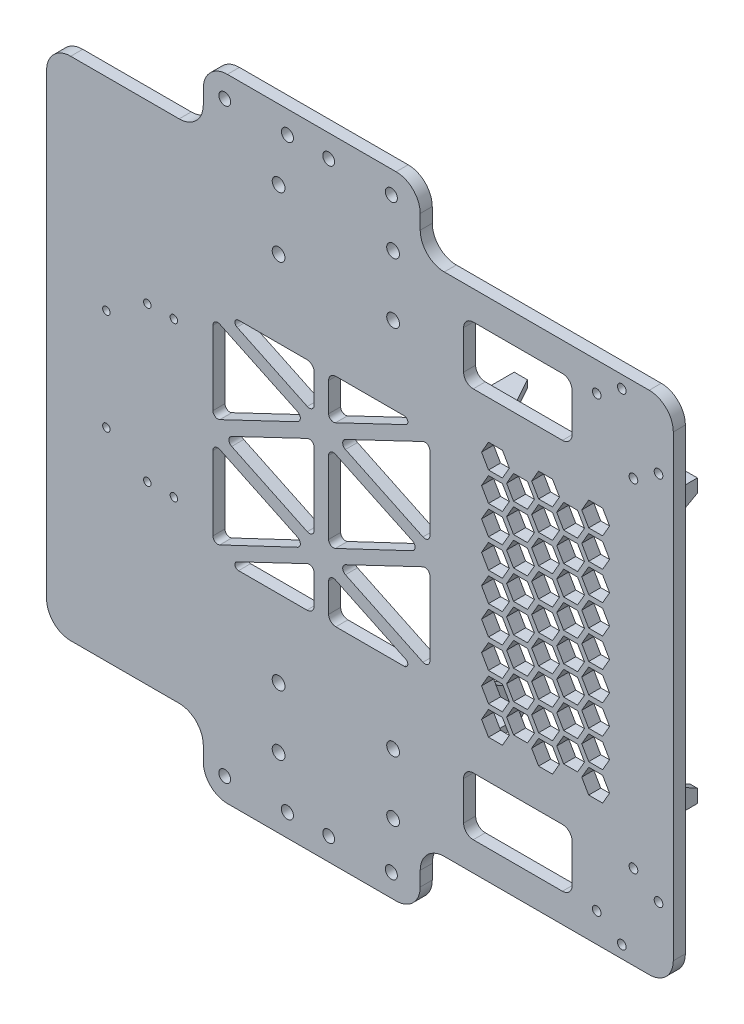
SolidWorks part; units mm, degrees
ref_plane "前视基准面" through (0, 0, 0) normal (0, 0, 1) x (1, 0, 0)
ref_plane "上视基准面" through (0, 0, 0) normal (0, 1, 0) x (1, 0, 0)
ref_plane "右视基准面" through (0, 0, 0) normal (1, 0, 0) x (0, 0, -1)
sketch "草图1" plane through (0, 0, 0) normal (0, 0, 1) x (1, 0, 0)
  line L2 (-130, 95) -> (-130, -95)
  line L3 (-120, -105) -> (-75, -105)
  line L4 (130, 95) -> (130, -95)
  line L5 (126.7518, 102.3765) -> (130, 105) construction
  line L6 (-130, -105) -> (-126.7518, -102.3765) construction
  line L9 (-65, -115) -> (-65, -121)
  line L10 (-55, -131) -> (15, -131)
  line L11 (25, -121) -> (25, -115)
  line L13 (35, -105) -> (120, -105)
  line L14 (126.7518, -102.3765) -> (130, -105) construction
  line L15 (-130, 105) -> (-126.7518, 102.3765) construction
  line L16 (-130, 0) -> (130, 0) construction
  line L17 (35, 105) -> (120, 105)
  line L18 (25, 121) -> (25, 115)
  line L19 (-55, 131) -> (15, 131)
  line L20 (-65, 115) -> (-65, 121)
  line L21 (-120, 105) -> (-75, 105)
  arc A1 (-120, -105) -> (-130, -95) centre (-120, -95) cw
  arc A3 (120, -105) -> (130, -95) centre (120, -95) ccw
  arc A8 (-65, -115) -> (-75, -105) centre (-75, -115) ccw
  arc A9 (25, -115) -> (35, -105) centre (35, -115) cw
  arc A10 (-55, -131) -> (-65, -121) centre (-55, -121) cw
  arc A11 (15, -131) -> (25, -121) centre (15, -121) ccw
  arc A12 (15, 131) -> (25, 121) centre (15, 121) cw
  arc A13 (-55, 131) -> (-65, 121) centre (-55, 121) ccw
  arc A14 (25, 115) -> (35, 105) centre (35, 115) ccw
  arc A15 (-65, 115) -> (-75, 105) centre (-75, 115) cw
  arc A16 (120, 105) -> (130, 95) centre (120, 95) cw
  arc A17 (-120, 105) -> (-130, 95) centre (-120, 95) ccw
  point P0 (0, 0)
  point P40 (25, -105)
  point P45 (25, 105)
  dimension "D2" = 10
  dimension "D3" = 65
  dimension "D4" = 10
  dimension "D5" = 105
  dimension "D7" = 10
  dimension "D8" = 10
  dimension "D10" = 10
  dimension "D12" = 10
  dimension "D13" = 105
  dimension "D18" = 90
  dimension "D19" = 6
extrude "凸台-拉伸1" add sketch "草图1" along normal blind 5
sketch "草图4" plane through (0, 0, 0) normal (0, 0, -1) x (-1, 0, 0)
  line L0 (-39, -47.5) -> (-39, -58.5)
  line L1 (-39, -58.5) -> (-50, -58.5)
  line L2 (-50, -58.5) -> (-50, -55.5)
  line L3 (-50, -55.5) -> (-42, -55.5)
  line L4 (-42, -55.5) -> (-42, -47.5)
  line L5 (-42, -47.5) -> (-39, -47.5)
  line L6 (-130, 0) -> (-25.5592, 0) construction
  line L7 (-130, -95) -> (-130, 95) construction
  line L10 (-130, -95) -> (-130, 95) construction
  dimension "D1" = 11
  dimension "D2" = 11
  dimension "D3" = 3
  dimension "D4" = 3
  dimension "D5" = 80
  dimension "D7" = 55.5
extrude "凸台-拉伸2" add sketch "草图4" along normal blind 20
sketch "草图5" plane through (0, -58.5, 0) normal (0, -1, 0) x (1, 0, 0)
  line L0 (50, -10) -> (44.5, -20)
  line L1 (50, -20) -> (50, 0) construction
  line L2 (50, -20) -> (39, -20) construction
  line L3 (44.5, -20) -> (50, -20)
  line L4 (50, -20) -> (50, -10)
  dimension "D1" = 10
  dimension "D2" = 5.5
extrude "切除-拉伸3" cut sketch "草图5" against normal blind 10
sketch "草图6" plane through (39, 0, 0) normal (-1, 0, 0) x (0, 0, 1)
  line L0 (-20, -53) -> (-10, -47.5)
  line L1 (-20, -58.5) -> (-20, -47.5) construction
  line L2 (-20, -47.5) -> (0, -47.5) construction
  line L3 (-10, -47.5) -> (-20, -47.5)
  line L4 (-20, -47.5) -> (-20, -53)
  dimension "D1" = 10
  dimension "D2" = 5.5
extrude "切除-拉伸4" cut sketch "草图6" against normal blind 10
ref_plane "基准面2" through (77, 0, 0) normal (1, 0, 0) x (0, 0, -1)
mirror "镜向1" about plane through (77, 0, 0) normal (1, 0, 0) of "凸台-拉伸2", "切除-拉伸4", "切除-拉伸3"
mirror "镜向2" about plane through (0, 0, 0) normal (0, 1, 0) of "镜向1"
sketch "草图7" plane through (0, 0, 0) normal (0, 0, -1) x (-1, 0, 0)
  line L4 (-112, -55.5) -> (-104, -55.5) construction
  line L5 (-112, 47.5) -> (-112, 55.5) construction
  line L6 (-112, 55.5) -> (-104, 55.5) construction
  line L7 (-92.013, 36) -> (-94.8997, 41)
  line L8 (-94.8997, 41) -> (-100.6732, 41)
  line L9 (-100.6732, 41) -> (-103.56, 36)
  line L10 (-103.56, 36) -> (-100.6732, 31)
  line L11 (-100.6732, 31) -> (-94.8997, 31)
  line L12 (-94.8997, 31) -> (-92.013, 36)
  line L13 (-77.0019, 36) -> (-97.7865, 36) construction
  line L14 (-74.1151, 31) -> (-71.2284, 36)
  line L15 (-71.2284, 36) -> (-74.1151, 41)
  line L16 (-74.1151, 41) -> (-79.8886, 41)
  line L17 (-79.8886, 41) -> (-82.7754, 36)
  line L18 (-82.7754, 36) -> (-79.8886, 31)
  line L19 (-79.8886, 31) -> (-74.1151, 31)
  line L20 (-92.013, 24) -> (-94.8997, 29)
  line L21 (-93.1677, 30) -> (-90.2809, 25)
  line L22 (-90.2809, 25) -> (-84.5074, 25)
  line L23 (-84.5074, 25) -> (-81.6207, 30)
  line L24 (-81.6207, 30) -> (-84.5074, 35)
  line L25 (-84.5074, 35) -> (-90.2809, 35)
  line L26 (-90.2809, 35) -> (-93.1677, 30)
  line L27 (-84.5074, 37) -> (-81.6207, 42)
  line L28 (-81.6207, 42) -> (-84.5074, 47)
  line L29 (-84.5074, 47) -> (-90.2809, 47)
  line L30 (-90.2809, 47) -> (-93.1677, 42)
  line L31 (-93.1677, 42) -> (-90.2809, 37)
  line L32 (-90.2809, 37) -> (-84.5074, 37)
  line L33 (-79.8886, 43) -> (-74.1151, 43)
  line L34 (-74.1151, 43) -> (-71.2284, 48)
  line L35 (-71.2284, 48) -> (-74.1151, 53)
  line L36 (-74.1151, 53) -> (-79.8886, 53)
  line L37 (-79.8886, 53) -> (-82.7754, 48)
  line L38 (-82.7754, 48) -> (-79.8886, 43)
  line L39 (-94.8997, 43) -> (-92.013, 48)
  line L40 (-92.013, 48) -> (-94.8997, 53)
  line L41 (-94.8997, 53) -> (-100.6732, 53)
  line L42 (-100.6732, 53) -> (-103.56, 48)
  line L43 (-103.56, 48) -> (-100.6732, 43)
  line L44 (-100.6732, 43) -> (-94.8997, 43)
  line L45 (-72.3831, 42) -> (-69.4963, 37)
  line L46 (-69.4963, 37) -> (-63.7228, 37)
  line L47 (-63.7228, 37) -> (-60.8361, 42)
  line L48 (-60.8361, 42) -> (-63.7228, 47)
  line L49 (-63.7228, 47) -> (-69.4963, 47)
  line L50 (-69.4963, 47) -> (-72.3831, 42)
  line L51 (-94.8997, 29) -> (-100.6732, 29)
  line L52 (-100.6732, 29) -> (-103.56, 24)
  line L53 (-103.56, 24) -> (-100.6732, 19)
  line L54 (-100.6732, 19) -> (-94.8997, 19)
  line L55 (-94.8997, 19) -> (-92.013, 24)
  line L56 (-93.1677, 18) -> (-90.2809, 13)
  line L57 (-90.2809, 13) -> (-84.5074, 13)
  line L58 (-84.5074, 13) -> (-81.6207, 18)
  line L59 (-81.6207, 18) -> (-84.5074, 23)
  line L60 (-84.5074, 23) -> (-90.2809, 23)
  line L61 (-90.2809, 23) -> (-93.1677, 18)
  line L62 (-74.1151, 19) -> (-71.2284, 24)
  line L63 (-71.2284, 24) -> (-74.1151, 29)
  line L64 (-74.1151, 29) -> (-79.8886, 29)
  line L65 (-79.8886, 29) -> (-82.7754, 24)
  line L66 (-82.7754, 24) -> (-79.8886, 19)
  line L67 (-79.8886, 19) -> (-74.1151, 19)
  line L68 (-72.3831, 30) -> (-69.4963, 25)
  line L69 (-69.4963, 25) -> (-63.7228, 25)
  line L70 (-63.7228, 25) -> (-60.8361, 30)
  line L71 (-60.8361, 30) -> (-63.7228, 35)
  line L72 (-63.7228, 35) -> (-69.4963, 35)
  line L73 (-69.4963, 35) -> (-72.3831, 30)
  line L74 (-92.013, 12) -> (-94.8997, 17)
  line L75 (-94.8997, 17) -> (-100.6732, 17)
  line L76 (-100.6732, 17) -> (-103.56, 12)
  line L77 (-103.56, 12) -> (-100.6732, 7)
  line L78 (-100.6732, 7) -> (-94.8997, 7)
  line L79 (-94.8997, 7) -> (-92.013, 12)
  line L80 (-93.1677, 6) -> (-90.2809, 1)
  line L81 (-90.2809, 1) -> (-84.5074, 1)
  line L82 (-84.5074, 1) -> (-81.6207, 6)
  line L83 (-81.6207, 6) -> (-84.5074, 11)
  line L84 (-84.5074, 11) -> (-90.2809, 11)
  line L85 (-90.2809, 11) -> (-93.1677, 6)
  line L86 (-74.1151, 7) -> (-71.2284, 12)
  line L87 (-71.2284, 12) -> (-74.1151, 17)
  line L88 (-74.1151, 17) -> (-79.8886, 17)
  line L89 (-79.8886, 17) -> (-82.7754, 12)
  line L90 (-82.7754, 12) -> (-79.8886, 7)
  line L91 (-79.8886, 7) -> (-74.1151, 7)
  line L92 (-72.3831, 18) -> (-69.4963, 13)
  line L93 (-69.4963, 13) -> (-63.7228, 13)
  line L94 (-63.7228, 13) -> (-60.8361, 18)
  line L95 (-60.8361, 18) -> (-63.7228, 23)
  line L96 (-63.7228, 23) -> (-69.4963, 23)
  line L97 (-69.4963, 23) -> (-72.3831, 18)
  line L98 (-92.013, 0) -> (-94.8997, 5)
  line L99 (-94.8997, 5) -> (-100.6732, 5)
  line L100 (-100.6732, 5) -> (-103.56, 0)
  line L101 (-103.56, 0) -> (-100.6732, -5)
  line L102 (-100.6732, -5) -> (-94.8997, -5)
  line L103 (-94.8997, -5) -> (-92.013, 0)
  line L104 (-93.1677, -6) -> (-90.2809, -11)
  line L105 (-90.2809, -11) -> (-84.5074, -11)
  line L106 (-84.5074, -11) -> (-81.6207, -6)
  line L107 (-81.6207, -6) -> (-84.5074, -1)
  line L108 (-84.5074, -1) -> (-90.2809, -1)
  line L109 (-90.2809, -1) -> (-93.1677, -6)
  line L110 (-74.1151, -5) -> (-71.2284, 0)
  line L111 (-71.2284, 0) -> (-74.1151, 5)
  line L112 (-74.1151, 5) -> (-79.8886, 5)
  line L113 (-79.8886, 5) -> (-82.7754, 0)
  line L114 (-82.7754, 0) -> (-79.8886, -5)
  line L115 (-79.8886, -5) -> (-74.1151, -5)
  line L116 (-72.3831, 6) -> (-69.4963, 1)
  line L117 (-69.4963, 1) -> (-63.7228, 1)
  line L118 (-63.7228, 1) -> (-60.8361, 6)
  line L119 (-60.8361, 6) -> (-63.7228, 11)
  line L120 (-63.7228, 11) -> (-69.4963, 11)
  line L121 (-69.4963, 11) -> (-72.3831, 6)
  line L122 (-92.013, -12) -> (-94.8997, -7)
  line L123 (-94.8997, -7) -> (-100.6732, -7)
  line L124 (-100.6732, -7) -> (-103.56, -12)
  line L125 (-103.56, -12) -> (-100.6732, -17)
  line L126 (-100.6732, -17) -> (-94.8997, -17)
  line L127 (-94.8997, -17) -> (-92.013, -12)
  line L128 (-93.1677, -18) -> (-90.2809, -23)
  line L129 (-90.2809, -23) -> (-84.5074, -23)
  line L130 (-84.5074, -23) -> (-81.6207, -18)
  line L131 (-81.6207, -18) -> (-84.5074, -13)
  line L132 (-84.5074, -13) -> (-90.2809, -13)
  line L133 (-90.2809, -13) -> (-93.1677, -18)
  line L134 (-74.1151, -17) -> (-71.2284, -12)
  line L135 (-71.2284, -12) -> (-74.1151, -7)
  line L136 (-74.1151, -7) -> (-79.8886, -7)
  line L137 (-79.8886, -7) -> (-82.7754, -12)
  line L138 (-82.7754, -12) -> (-79.8886, -17)
  line L139 (-79.8886, -17) -> (-74.1151, -17)
  line L140 (-72.3831, -6) -> (-69.4963, -11)
  line L141 (-69.4963, -11) -> (-63.7228, -11)
  line L142 (-63.7228, -11) -> (-60.8361, -6)
  line L143 (-60.8361, -6) -> (-63.7228, -1)
  line L144 (-63.7228, -1) -> (-69.4963, -1)
  line L145 (-69.4963, -1) -> (-72.3831, -6)
  line L146 (-92.013, -24) -> (-94.8997, -19)
  line L147 (-94.8997, -19) -> (-100.6732, -19)
  line L148 (-100.6732, -19) -> (-103.56, -24)
  line L149 (-103.56, -24) -> (-100.6732, -29)
  line L150 (-100.6732, -29) -> (-94.8997, -29)
  line L151 (-94.8997, -29) -> (-92.013, -24)
  line L152 (-93.1677, -30) -> (-90.2809, -35)
  line L153 (-90.2809, -35) -> (-84.5074, -35)
  line L154 (-84.5074, -35) -> (-81.6207, -30)
  line L155 (-81.6207, -30) -> (-84.5074, -25)
  line L156 (-84.5074, -25) -> (-90.2809, -25)
  line L157 (-90.2809, -25) -> (-93.1677, -30)
  line L158 (-74.1151, -29) -> (-71.2284, -24)
  line L159 (-71.2284, -24) -> (-74.1151, -19)
  line L160 (-74.1151, -19) -> (-79.8886, -19)
  line L161 (-79.8886, -19) -> (-82.7754, -24)
  line L162 (-82.7754, -24) -> (-79.8886, -29)
  line L163 (-79.8886, -29) -> (-74.1151, -29)
  line L164 (-72.3831, -18) -> (-69.4963, -23)
  line L165 (-69.4963, -23) -> (-63.7228, -23)
  line L166 (-63.7228, -23) -> (-60.8361, -18)
  line L167 (-60.8361, -18) -> (-63.7228, -13)
  line L168 (-63.7228, -13) -> (-69.4963, -13)
  line L169 (-69.4963, -13) -> (-72.3831, -18)
  line L170 (-92.013, -36) -> (-94.8997, -31)
  line L171 (-94.8997, -31) -> (-100.6732, -31)
  line L172 (-100.6732, -31) -> (-103.56, -36)
  line L173 (-103.56, -36) -> (-100.6732, -41)
  line L174 (-100.6732, -41) -> (-94.8997, -41)
  line L175 (-94.8997, -41) -> (-92.013, -36)
  line L176 (-93.1677, -42) -> (-90.2809, -47)
  line L177 (-90.2809, -47) -> (-84.5074, -47)
  line L178 (-84.5074, -47) -> (-81.6207, -42)
  line L179 (-81.6207, -42) -> (-84.5074, -37)
  line L180 (-84.5074, -37) -> (-90.2809, -37)
  line L181 (-90.2809, -37) -> (-93.1677, -42)
  line L182 (-74.1151, -41) -> (-71.2284, -36)
  line L183 (-71.2284, -36) -> (-74.1151, -31)
  line L184 (-74.1151, -31) -> (-79.8886, -31)
  line L185 (-79.8886, -31) -> (-82.7754, -36)
  line L186 (-82.7754, -36) -> (-79.8886, -41)
  line L187 (-79.8886, -41) -> (-74.1151, -41)
  line L188 (-72.3831, -30) -> (-69.4963, -35)
  line L189 (-69.4963, -35) -> (-63.7228, -35)
  line L190 (-63.7228, -35) -> (-60.8361, -30)
  line L191 (-60.8361, -30) -> (-63.7228, -25)
  line L192 (-63.7228, -25) -> (-69.4963, -25)
  line L193 (-69.4963, -25) -> (-72.3831, -30)
  line L194 (-92.013, -48) -> (-94.8997, -43)
  line L195 (-94.8997, -43) -> (-100.6732, -43)
  line L196 (-100.6732, -43) -> (-103.56, -48)
  line L197 (-103.56, -48) -> (-100.6732, -53)
  line L198 (-100.6732, -53) -> (-94.8997, -53)
  line L199 (-94.8997, -53) -> (-92.013, -48)
  line L206 (-74.1151, -53) -> (-71.2284, -48)
  line L207 (-71.2284, -48) -> (-74.1151, -43)
  line L208 (-74.1151, -43) -> (-79.8886, -43)
  line L209 (-79.8886, -43) -> (-82.7754, -48)
  line L210 (-82.7754, -48) -> (-79.8886, -53)
  line L211 (-79.8886, -53) -> (-74.1151, -53)
  line L212 (-72.3831, -42) -> (-69.4963, -47)
  line L213 (-69.4963, -47) -> (-63.7228, -47)
  line L214 (-63.7228, -47) -> (-60.8361, -42)
  line L215 (-60.8361, -42) -> (-63.7228, -37)
  line L216 (-63.7228, -37) -> (-69.4963, -37)
  line L217 (-69.4963, -37) -> (-72.3831, -42)
  line L218 (-61.9908, 36) -> (-59.104, 31)
  line L219 (-61.9908, 48) -> (-59.104, 43)
  line L220 (-59.104, 43) -> (-53.3305, 43)
  line L221 (-53.3305, 43) -> (-50.4438, 48)
  line L222 (-50.4438, 48) -> (-53.3305, 53)
  line L223 (-53.3305, 53) -> (-59.104, 53)
  line L224 (-59.104, 53) -> (-61.9908, 48)
  line L225 (-59.104, 31) -> (-53.3305, 31)
  line L226 (-53.3305, 31) -> (-50.4438, 36)
  line L227 (-50.4438, 36) -> (-53.3305, 41)
  line L228 (-53.3305, 41) -> (-59.104, 41)
  line L229 (-59.104, 41) -> (-61.9908, 36)
  line L230 (-61.9908, 24) -> (-59.104, 19)
  line L231 (-59.104, 19) -> (-53.3305, 19)
  line L232 (-53.3305, 19) -> (-50.4438, 24)
  line L233 (-50.4438, 24) -> (-53.3305, 29)
  line L234 (-53.3305, 29) -> (-59.104, 29)
  line L235 (-59.104, 29) -> (-61.9908, 24)
  line L236 (-61.9908, 12) -> (-59.104, 7)
  line L237 (-59.104, 7) -> (-53.3305, 7)
  line L238 (-53.3305, 7) -> (-50.4438, 12)
  line L239 (-50.4438, 12) -> (-53.3305, 17)
  line L240 (-53.3305, 17) -> (-59.104, 17)
  line L241 (-59.104, 17) -> (-61.9908, 12)
  line L242 (-61.9908, 0) -> (-59.104, -5)
  line L243 (-59.104, -5) -> (-53.3305, -5)
  line L244 (-53.3305, -5) -> (-50.4438, 0)
  line L245 (-50.4438, 0) -> (-53.3305, 5)
  line L246 (-53.3305, 5) -> (-59.104, 5)
  line L247 (-59.104, 5) -> (-61.9908, 0)
  line L248 (-61.9908, -12) -> (-59.104, -17)
  line L249 (-59.104, -17) -> (-53.3305, -17)
  line L250 (-53.3305, -17) -> (-50.4438, -12)
  line L251 (-50.4438, -12) -> (-53.3305, -7)
  line L252 (-53.3305, -7) -> (-59.104, -7)
  line L253 (-59.104, -7) -> (-61.9908, -12)
  line L254 (-61.9908, -24) -> (-59.104, -29)
  line L255 (-59.104, -29) -> (-53.3305, -29)
  line L256 (-53.3305, -29) -> (-50.4438, -24)
  line L257 (-50.4438, -24) -> (-53.3305, -19)
  line L258 (-53.3305, -19) -> (-59.104, -19)
  line L259 (-59.104, -19) -> (-61.9908, -24)
  line L260 (-61.9908, -36) -> (-59.104, -41)
  line L261 (-59.104, -41) -> (-53.3305, -41)
  line L262 (-53.3305, -41) -> (-50.4438, -36)
  line L263 (-50.4438, -36) -> (-53.3305, -31)
  line L264 (-53.3305, -31) -> (-59.104, -31)
  line L265 (-59.104, -31) -> (-61.9908, -36)
  line L266 (-61.9908, -48) -> (-59.104, -53)
  line L267 (-59.104, -53) -> (-53.3305, -53)
  line L268 (-53.3305, -53) -> (-50.4438, -48)
  line L269 (-50.4438, -48) -> (-53.3305, -43)
  line L270 (-53.3305, -43) -> (-59.104, -43)
  line L271 (-59.104, -43) -> (-61.9908, -48)
  line L272 (-93.1677, -54) -> (-90.2809, -59) [skipped]
  line L273 (-90.2809, -59) -> (-84.5074, -59) [skipped]
  line L274 (-84.5074, -59) -> (-81.6207, -54) [skipped]
  line L275 (-81.6207, -54) -> (-84.5074, -49) [skipped]
  line L276 (-84.5074, -49) -> (-90.2809, -49) [skipped]
  line L277 (-90.2809, -49) -> (-93.1677, -54) [skipped]
  circle A0 centre (-97.7865, 36) radius 5 construction
  circle A1 centre (-77.0019, 36) radius 5 construction
  circle A2 centre (-87.3942, 30) radius 5 construction
  circle A3 centre (-87.3942, 42) radius 5 construction
  circle A4 centre (-77.0019, 48) radius 5 construction
  circle A5 centre (-97.7865, 48) radius 5 construction
  circle A6 centre (-66.6096, 42) radius 5 construction
  circle A7 centre (-56.2173, 48) radius 5 construction
  point P4 (-87.3942, 37)
  dimension "D1" = 2
  dimension "D3" = 10
  dimension "D4" = 10
  dimension "D5" = 2
  dimension "D7" = 10
  dimension "D11" = 10
  dimension "D14" = 10
  dimension "D15" = 10
  dimension "D20" = 10
  dimension "D2" = 2
  dimension "D6" = 2
  dimension "D8" = 2
  dimension "D9" = 2
  dimension "D10" = 2
  dimension "D12" = 2
  dimension "D13" = 2
  dimension "D16" = 2
  dimension "D17" = 2
  dimension "D19" = 2
  dimension "D21" = 9
  dimension "D22" = 2.5
  dimension "D23" = 2.5
  dimension "D24" = 8.44
  dimension "D18" = 8
extrude "切除-拉伸5" cut sketch "草图7" against normal blind 5
sketch "草图8" plane through (0, 0, 0) normal (0, 0, -1) x (-1, 0, 0)
  line L0 (-75.3677, 120) -> (-75.3677, -120)
  line L1 (-100.0285, 77.2863) -> (-100.0285, -77.2863)
  line L2 (-100.0285, 77.2863) -> (-75.3677, 120)
  line L3 (-100.0285, -77.2863) -> (-75.3677, -120)
  line L4 (-37.1297, 0) -> (-146.8562, 0) construction
  dimension "D1" = 30
  dimension "D2" = 30
  dimension "D3" = 120
  dimension "D4" = 120
sketch "草图9" plane through (0, 0, 0) normal (0, 0, -1) x (-1, 0, 0)
  line L0 (148.8518, 0) -> (-37.1297, 0) construction
  line L1 (-29, 41) -> (-29, 4)
  line L2 (-25, -45) -> (13, -45)
  line L3 (61, -41) -> (61, -4)
  line L4 (57, 45) -> (19, 45)
  line L14 (-29, 41) -> (9.8049, 22.5)
  line L15 (57, 0) -> (19, -18.1163)
  line L16 (130, 95) -> (130, -95) construction
  line L17 (63, 93) -> (118, 93)
  line L18 (63, 93) -> (63, 66)
  line L19 (63, 66) -> (118, 66)
  line L20 (118, 93) -> (118, 66)
  line L21 (75, 105) -> (120, 105) construction
  line L22 (63, -66) -> (118, -66)
  line L23 (118, -93) -> (118, -66)
  line L24 (63, -93) -> (118, -93)
  line L25 (63, -93) -> (63, -66)
  line L26 (-120, 105) -> (-35, 105) construction
  line L27 (-43, 93) -> (-88, 93)
  line L28 (-43, 93) -> (-43, 69)
  line L29 (-43, 69) -> (-88, 69)
  line L30 (-88, 93) -> (-88, 69)
  line L31 (-130, -95) -> (-130, 95) construction
  line L32 (-43, -69) -> (-88, -69)
  line L33 (-88, -93) -> (-88, -69)
  line L34 (-43, -93) -> (-88, -93)
  line L35 (-43, -93) -> (-43, -69)
  line L36 (-25, 45) -> (13, 26.8837)
  line L37 (-25, -45) -> (13, -26.8837)
  line L38 (61, 41) -> (22.0746, 22.5575)
  line L39 (-25.5359, 0) -> (13, -18.258)
  line L40 (57, 45) -> (19, 26.8837)
  line L41 (57, -45) -> (19, -26.8837)
  line L42 (16, 61.4977) -> (16, -60.5731) construction
  line L43 (13, 45) -> (13, 26.8837)
  line L44 (19, 45) -> (19, 26.8837)
  line L45 (13, 18.258) -> (13, -18.258)
  line L46 (9.8049, 22.5) -> (-29, 4)
  line L47 (19, 18.1163) -> (57, 0)
  line L48 (22.0746, 22.5575) -> (61, 4)
  line L49 (13, 18.258) -> (-25.5359, 0)
  line L50 (19, 18.1163) -> (19, -18.1163)
  line L51 (22.0746, -22.5575) -> (61, -41)
  line L52 (9.8049, -22.5) -> (-29, -41)
  line L53 (9.8049, -22.5) -> (-29, -4)
  line L54 (22.0746, -22.5575) -> (61, -4)
  line L55 (13, -26.8837) -> (13, -45)
  line L56 (19, -26.8837) -> (19, -45)
  line L57 (13, 45) -> (-25, 45)
  line L58 (-29, -4) -> (-29, -41)
  line L59 (19, -45) -> (57, -45)
  line L60 (61, 4) -> (61, 41)
  line L61 (-44, 41) -> (-44, -37.8122) construction
  dimension "D1" = 45
  dimension "D2" = 45
  dimension "D3" = 15
  dimension "D4" = 90
  dimension "D5" = 1
  dimension "D7" = 12
  dimension "D8" = 12
  dimension "D9" = 27
  dimension "D10" = 55
  dimension "D11" = 12
  dimension "D12" = 45
  dimension "D13" = 42
  dimension "D14" = 24
  dimension "D21" = 4
  dimension "D22" = 4
  dimension "D23" = 4
  dimension "D24" = 4
  dimension "D26" = 4
  dimension "D27" = 3
  dimension "D28" = 45
extrude "切除-拉伸6" cut sketch "草图9" against normal blind 5 contours L27 L30 L29 L28 | L34 L35 L32 L33 | L4 L44 L40 | L48 L60 L38 | L47 L50 L15 | L54 L51 L3 | L56 L59 L41 | L55 L37 L2 | L53 L58 L52 | L45 L49 L39 | L46 L14 L1 | L43 L57 L36 | L57 L36 L43 region at (16.065, 22.5, 0) region at (-0.3333, -38.9612, 0) region at (-48.0249, -22.5192, 0) region at (-31.6667, 38.9612, 0) region at (-31.6667, 0, 0) region at (65.5, 81, 0) region at (65.5, -81, 0) region at (-0.3333, 38.9612, 0) region at (-48.0249, 22.5192, 0) region at (-0.1547, 0, 0) region at (-31.6667, -38.9612, 0) region at (16.065, -22.5, 0)
fillet "圆角1" radius 4 8 edges at (43, -93, 2.5) (88, -69, 2.5) (43, -69, 2.5) (88, -93, 2.5) (88, 69, 2.5) (43, 69, 2.5) (43, 93, 2.5) (88, 93, 2.5)
fillet "圆角2" radius 1.5 4 edges at (25, -45, 2.5) (-57, -45, 2.5) (25, 45, 2.5) (-57, 45, 2.5)
fillet "圆角3" radius 2 22 edges at (29, -4, 2.5) (29, 4, 2.5) (-13, -18.258, 2.5) (-61, -41, 2.5) (-61, 4, 2.5) (-13, -26.8837, 2.5) (-13, 18.258, 2.5) (-61, -4, 2.5) (-22.0746, -22.5575, 2.5) (25.5359, 0, 2.5) (-22.0746, 22.5575, 2.5) (-61, 41, 2.5) (-19, 26.8837, 2.5) (-19, -26.8837, 2.5) (-19, -18.1163, 2.5) (29, -41, 2.5) (29, 41, 2.5) (-57, 0, 2.5) (-9.8049, -22.5, 2.5) (-13, 26.8837, 2.5) (-9.8049, 22.5, 2.5) (-19, 18.1163, 2.5)
fillet "圆角4" radius 3 4 edges at (-13, -45, 2.5) (-13, 45, 2.5) (-19, -45, 2.5) (-19, 45, 2.5)
sketch "草图10" plane through (0, 0, 0) normal (0, 0, -1) x (-1, 0, 0)
  line L0 (-37.1297, 0) -> (-146.8562, 0) construction
  line L1 (-37.1297, 0) -> (-146.8562, 0) construction
  circle A0 centre (-123.8743, 76.9597) radius 1.8 construction
  circle A1 centre (-113.4687, 70.0334) radius 1.8 construction
  circle A2 centre (-108.6364, 99.852) radius 1.8 construction
  circle A3 centre (-98.2308, 92.9256) radius 1.8 construction
  circle A4 centre (105.2101, 21) radius 1.55 construction
  circle A5 centre (88.2101, 32) radius 1.55 construction
  circle A6 centre (77.2101, 32) radius 1.55 construction
  circle A7 centre (33.75, 102) radius 2.65 construction
  circle A8 centre (33.75, 77) radius 2.65 construction
  circle A9 centre (-13.75, 77) radius 2.65 construction
  circle A10 centre (-13.75, 102) radius 2.65 construction
  circle A11 centre (-13.0267, 121.679) radius 2.5 construction
  circle A12 centre (56.0941, 121.679) radius 2.45 construction
  circle A13 centre (30.0941, 121.679) radius 2.5 construction
  circle A14 centre (12.9733, 121.679) radius 2.45 construction
  circle A15 centre (-123.8743, 76.9597) radius 1.8
  circle A16 centre (-113.4687, 70.0334) radius 1.8
  circle A17 centre (-108.6364, 99.852) radius 1.8
  circle A18 centre (-98.2308, 92.9256) radius 1.8
  circle A19 centre (105.2101, 21) radius 1.55
  circle A20 centre (88.2101, 32) radius 1.55
  circle A21 centre (77.2101, 32) radius 1.55
  circle A22 centre (33.75, 102) radius 2.65
  circle A23 centre (33.75, 77) radius 2.65
  circle A24 centre (-13.75, 77) radius 2.65
  circle A25 centre (-13.75, 102) radius 2.65
  circle A26 centre (-13.0267, 121.679) radius 2.5
  circle A27 centre (56.0941, 121.679) radius 2.45
  circle A28 centre (30.0941, 121.679) radius 2.5
  circle A29 centre (12.9733, 121.679) radius 2.45
  circle A30 centre (12.9733, -121.679) radius 2.45
  circle A31 centre (30.0941, -121.679) radius 2.5
  circle A32 centre (56.0941, -121.679) radius 2.45
  circle A33 centre (-13.0267, -121.679) radius 2.5
  circle A34 centre (-13.75, -102) radius 2.65
  circle A35 centre (-13.75, -77) radius 2.65
  circle A36 centre (33.75, -77) radius 2.65
  circle A37 centre (33.75, -102) radius 2.65
  circle A38 centre (77.2101, -32) radius 1.55
  circle A39 centre (88.2101, -32) radius 1.55
  circle A40 centre (105.2101, -21) radius 1.55
  circle A41 centre (-98.2308, -92.9256) radius 1.8
  circle A42 centre (-108.6364, -99.852) radius 1.8
  circle A43 centre (-113.4687, -70.0334) radius 1.8
  circle A44 centre (-123.8743, -76.9597) radius 1.8
extrude "切除-拉伸7" cut sketch "草图10" against normal through all
equation "\"45、\"=43.7672"
